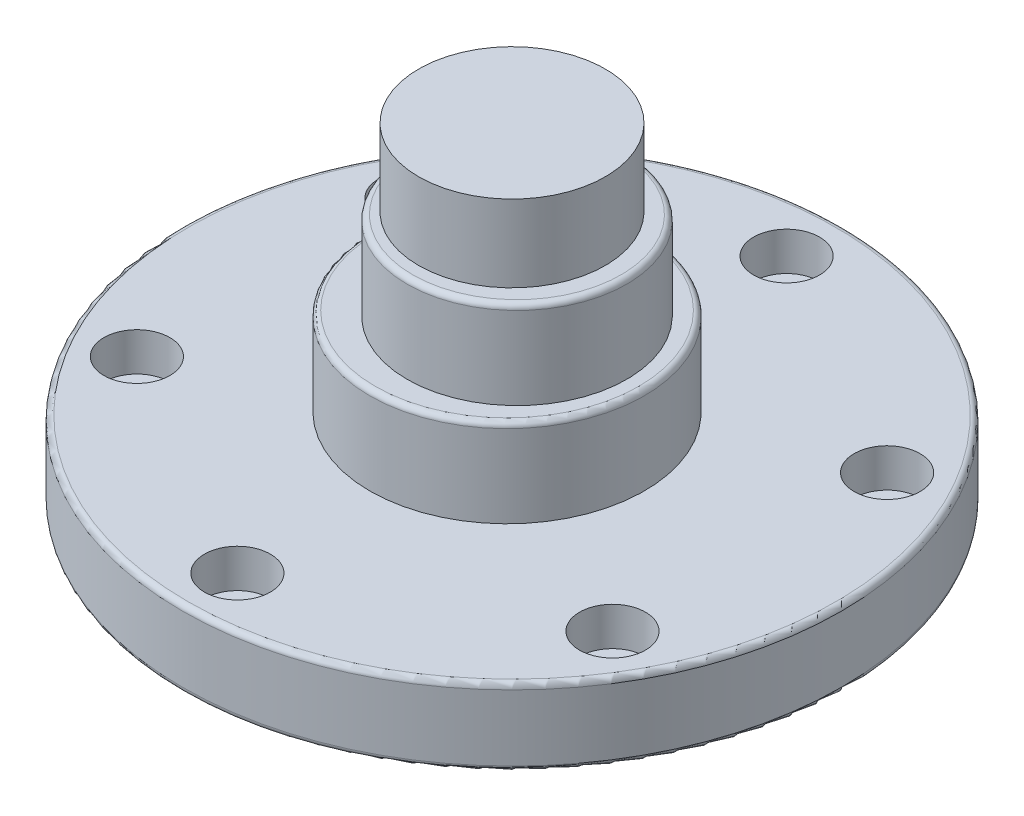
SolidWorks part; units mm, degrees
ref_plane "Front Plane" through (0, 0, 0) normal (0, 0, 1) x (1, 0, 0)
ref_plane "Top Plane" through (0, 0, 0) normal (0, 1, 0) x (1, 0, 0)
ref_plane "Right Plane" through (0, 0, 0) normal (1, 0, 0) x (0, 0, -1)
sketch "Sketch1" plane through (0, 0, 0) normal (0, 1, 0) x (1, 0, 0)
  circle A0 centre (0, 0) radius 25 construction
  circle A1 centre (0, 0) radius 30
  circle A2 centre (0, 25) radius 1.65
  circle A3 centre (21.6506, 12.5) radius 1.65
  circle A4 centre (21.6506, -12.5) radius 1.65
  circle A5 centre (0, -25) radius 1.65
  circle A6 centre (-21.6506, -12.5) radius 1.65
  circle A7 centre (-21.6506, 12.5) radius 1.65
  point P18 (0, 0)
  dimension "D1" = 50
  dimension "D2" = 60
  dimension "D3" = 3.3
  dimension "D4" = 6
extrude "Boss-Extrude1" add sketch "Sketch1" along normal blind 7
sketch "Sketch2" plane through (0, 7, 0) normal (0, 1, 0) x (1, 0, 0)
  circle A0 centre (-0.45, 0) radius 12.5
  point P0 (0, 0)
  point P1 (-0.45, 0)
  dimension "D2" = 25
  dimension "D1" = 0.45
extrude "Boss-Extrude2" add sketch "Sketch2" along normal blind 8
sketch "Sketch3" plane through (0, 15, 0) normal (0, 1, 0) x (1, 0, 0)
  circle A0 centre (0.45, 0) radius 10
  point P0 (0.45, 0)
  dimension "D2" = 20
  dimension "D1" = 0.45
extrude "Boss-Extrude3" add sketch "Sketch3" along normal blind 8
fillet "Fillet1" radius 0.5 4 edges at (0.45, 23, 10) (-0.45, 15, 12.5) (0, 0, 30) (0, 7, 30)
sketch "Sketch4" plane through (0, 7, 0) normal (0, 1, 0) x (1, 0, 0)
  circle A0 centre (0, 25) radius 3
  circle A1 centre (21.6506, 12.5) radius 3
  circle A2 centre (21.6506, -12.5) radius 3
  circle A3 centre (0, -25) radius 3
  circle A4 centre (-21.6506, -12.5) radius 3
  circle A5 centre (-21.6506, 12.5) radius 3
  point P16 (0, 0)
  dimension "D1" = 6
  dimension "D2" = 6
extrude "Cut-Extrude1" cut sketch "Sketch4" against normal blind 3.5
sketch "Sketch5" plane through (0, 23, 0) normal (0, 1, 0) x (1, 0, 0)
  circle A0 centre (0, 0) radius 8.5
  dimension "D1" = 17
extrude "Boss-Extrude4" add sketch "Sketch5" along normal blind 7
